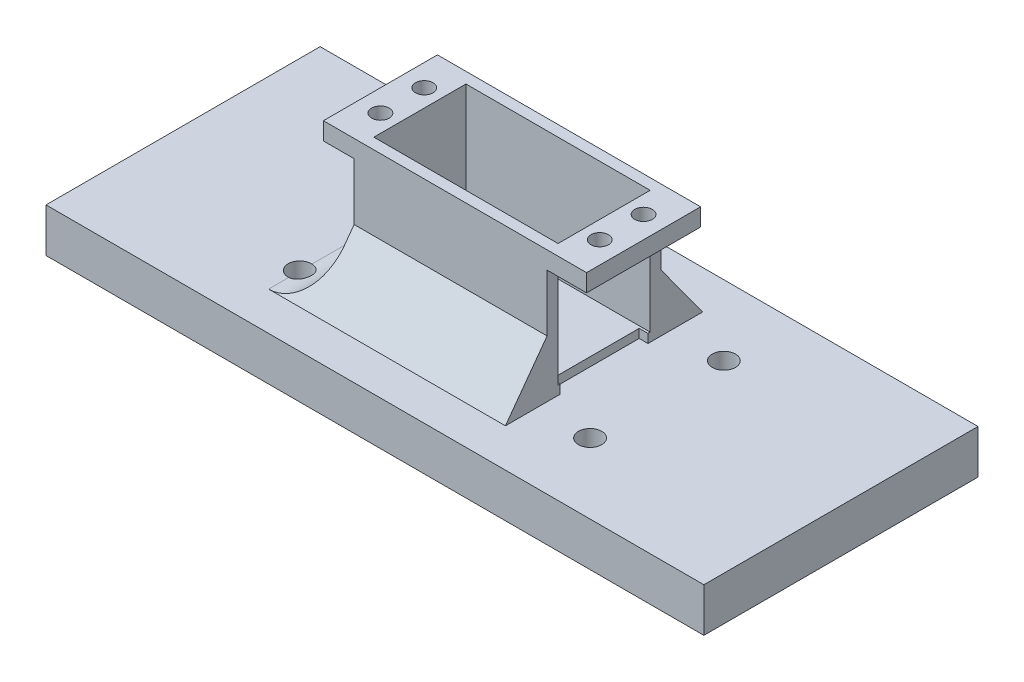
SolidWorks part; units mm, degrees
ref_plane "Front Plane" through (0, 0, 0) normal (0, 0, 1) x (1, 0, 0)
ref_plane "Top Plane" through (0, 0, 0) normal (0, 1, 0) x (1, 0, 0)
ref_plane "Right Plane" through (0, 0, 0) normal (1, 0, 0) x (0, 0, -1)
sketch "Sketch2" plane through (0, 0, 0) normal (0, 1, 0) x (1, 0, 0)
  line L0 (-75, 31.25) -> (-75, 15.25)
  line L1 (75, -31.25) -> (-75, -31.25)
  line L2 (75, -31.25) -> (75, 31.25)
  line L3 (75, 31.25) -> (-75, 31.25)
  line L4 (-75, -31.25) -> (-75, 31.25)
  line L5 (75, -31.25) -> (-75, 31.25) construction
  line L6 (75, 31.25) -> (-75, -31.25) construction
  line L7 (-75, 31.1391) -> (-33.13, 31.1391)
  line L8 (-75, 31.1391) -> (-24, 31.1391)
  line L9 (-75, -31.25) -> (-75, -15.25)
  line L10 (-75.0024, -31.25) -> (-75.0024, -15.25)
  line L15 (75.0334, 31.25) -> (75.0334, 15.25)
  line L16 (75, 31.25) -> (24, 31.25)
  line L17 (75.0334, 31.25) -> (33.05, 31.25)
  line L19 (75, -31.25) -> (24, -31.25)
  circle A0 centre (-33.13, 15.25) radius 2.65
  circle A1 centre (-33.13, -15.25) radius 2.65
  circle A2 centre (33.05, 15.25) radius 2.65
  circle A3 centre (33.05, -15.25) radius 2.65
  point P0 (0, 0)
  dimension "D7" = 16
  dimension "D8" = 5.3
  dimension "D9" = 5.3
  dimension "D10" = 5.3
  dimension "D11" = 5.3
  dimension "D1" = 150
  dimension "D2" = 62.5
  dimension "D3" = 16
  dimension "D4" = 41.87
  dimension "D5" = 51
  dimension "D6" = 16
extrude "Boss-Extrude1" add sketch "Sketch2" along normal blind 10 contours L4 L1 L2 L3 L16 L0 A3 A2 A1 A0 region at (0.0004, 0, 0)
sketch "Sketch4" plane through (0, 10, 0) normal (0, 1, 0) x (1, 0, 0)
  line L5 (30, -13) -> (-30, -13)
  line L6 (30, -13) -> (30, 13)
  line L7 (30, 13) -> (-30, 13)
  line L8 (-30, -13) -> (-30, 13)
  line L9 (30, -13) -> (-30, 13) construction
  line L10 (30, 13) -> (-30, -13) construction
  point P0 (0, 0)
  point P1 (0, 0)
  dimension "D1" = 60
  dimension "D2" = 26
  dimension "D3" = 60
extrude "Boss-Extrude2" add sketch "Sketch4" along normal blind 30
sketch "Sketch5" plane through (0, 40, 0) normal (0, 1, 0) x (1, 0, 0)
  line L1 (21, -10.5) -> (-21, -10.5)
  line L2 (21, -10.5) -> (21, 10.5)
  line L3 (21, 10.5) -> (-21, 10.5)
  line L4 (-21, -10.5) -> (-21, 10.5)
  line L5 (21, -10.5) -> (-21, 10.5) construction
  line L6 (21, 10.5) -> (-21, -10.5) construction
  line L7 (-21, 10.5) -> (-28, 10.5)
  line L8 (-28, 10.5) -> (-28, -10.5)
  line L9 (-28, -10.5) -> (-21, -10.5)
  point P0 (0, 0)
  dimension "D1" = 42
  dimension "D2" = 21
extrude "Cut-Extrude2" cut sketch "Sketch5" against normal blind 28 contours L4 L1 L2 L3 region at (0, 40, 0)
sketch "Sketch13" plane through (-30, 0, 0) normal (-1, 0, 0) x (0, 0, 1)
  line L0 (-13, 40) -> (-13, 10) construction
  line L1 (-13, 36) -> (13, 36)
  line L2 (-13, 36) -> (-13, 10)
  line L3 (-13, 10) -> (13, 10)
  line L4 (13, 36) -> (13, 10)
  dimension "D1" = 26
extrude "Cut-Extrude5" cut sketch "Sketch13" against normal blind 7
sketch "Sketch14" plane through (30, 0, 0) normal (1, 0, 0) x (0, 0, -1)
  line L0 (-13, 40) -> (-13, 10) construction
  line L1 (-13, 36) -> (13, 36)
  line L2 (-13, 36) -> (-13, 10)
  line L3 (-13, 10) -> (13, 10)
  line L4 (13, 36) -> (13, 10)
  dimension "D1" = 26
extrude "Cut-Extrude6" cut sketch "Sketch14" against normal blind 7
sketch "Sketch21" plane through (-23, 0, 0) normal (-1, 0, 0) x (0, 0, 1)
  line L0 (-13, 10) -> (-22.5, 10)
  line L1 (31.25, 10) -> (-31.25, 10) construction
  line L2 (-22.5, 10) -> (-13, 23)
  line L3 (-13, 36) -> (-13, 10) construction
  line L4 (-13, 23) -> (-13, 10)
  line L5 (13, 10) -> (22.5, 10)
  line L6 (22.5, 10) -> (13, 23)
  line L7 (13, 10) -> (13, 36) construction
  line L8 (13, 10) -> (13, 23)
extrude "Boss-Extrude4" add sketch "Sketch21" against normal blind 44
sketch "Sketch25" plane through (23, 0, 0) normal (1, 0, 0) x (0, 0, -1)
  line L1 (10, 32) -> (-10, 32)
  line L2 (10, 32) -> (10, 10)
  line L3 (10, 10) -> (-10, 10)
  line L4 (-10, 32) -> (-10, 10)
  line L5 (10, 32) -> (-10, 10) construction
  line L6 (10, 10) -> (-10, 32) construction
  line L10 (-13, 10) -> (13, 10) construction
  point P0 (0, 21)
  dimension "D1" = 0
  dimension "D2" = 22
  dimension "D3" = 20
extrude "Cut-Extrude10" cut sketch "Sketch25" against normal blind 4
fillet "Fillet1" radius 10 1 edges at (-23, 10, 0)
sketch "Sketch26" plane through (0, 40, 0) normal (0, 1, 0) x (1, 0, 0)
  circle A0 centre (-25, 5) radius 2
  circle A1 centre (-25, -5) radius 2
  circle A2 centre (25, -5) radius 2
  circle A3 centre (25, 5) radius 2
  point P0 (0, 0)
  dimension "D1" = 50
  dimension "D2" = 10
extrude "Cut-Extrude11" cut sketch "Sketch26" against normal blind 10
sketch "Sketch27" plane through (0, 0, 13) normal (0, 0, 1) x (1, 0, 0)
  line L1 (23, 36) -> (21, 36)
  line L2 (23, 36) -> (23, 10)
  line L3 (23, 10) -> (21, 10)
  line L4 (21, 36) -> (21, 10)
extrude "Cut-Extrude12" cut sketch "Sketch27" against normal blind 26
sketch "Sketch29" plane through (-23, 0, 0) normal (-1, 0, 0) x (0, 0, 1)
  line L0 (13, 36) -> (5, 36) construction
  line L1 (8.1416, 36) -> (2.3615, 36)
  line L2 (8.1416, 36) -> (8.1416, 29.2938)
  line L3 (8.1416, 29.2938) -> (2.3615, 29.2938)
  line L4 (2.3615, 36) -> (2.3615, 29.2938)
  line L5 (5, 36) -> (-5, 36) construction
  line L6 (-1.9201, 36) -> (-7.7013, 36)
  line L7 (-1.9201, 36) -> (-1.9201, 29.2938)
  line L8 (-1.9201, 29.2938) -> (-7.7013, 29.2938)
  line L9 (-7.7013, 36) -> (-7.7013, 29.2938)
  dimension "D1" = 5.7801
  dimension "D2" = 5.7812
  dimension "D3" = 6.7062
  dimension "D4" = 6.7062
extrude "Cut-Extrude13" cut sketch "Sketch29" against normal blind 1
